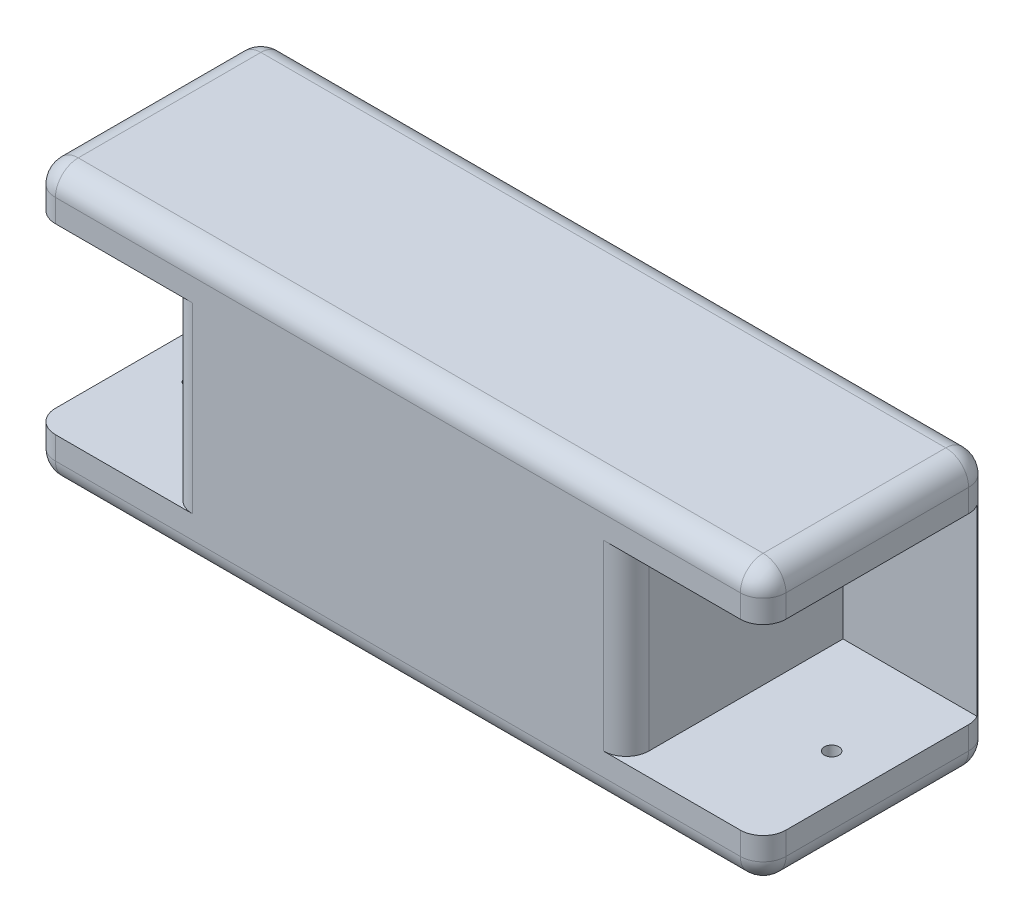
SolidWorks part; units mm, degrees
ref_plane "Front Plane" through (0, 0, 0) normal (0, 0, 1) x (1, 0, 0)
ref_plane "Top Plane" through (0, 0, 0) normal (0, 1, 0) x (1, 0, 0)
ref_plane "Right Plane" through (0, 0, 0) normal (1, 0, 0) x (0, 0, -1)
sketch "Sketch2" plane through (0, 0, 0) normal (0, 0, 1) x (1, 0, 0)
  line L1 (-80, 30) -> (80, 30)
  line L2 (-80, 30) -> (-80, -30)
  line L3 (-80, -30) -> (80, -30)
  line L4 (80, 30) -> (80, -30)
  line L5 (-80, 30) -> (80, -30) construction
  line L6 (-80, -30) -> (80, 30) construction
  point P0 (0, 0)
  dimension "D1" = 160
  dimension "D2" = 60
extrude "Boss-Extrude1" add sketch "Sketch2" along normal blind 50
sketch "Sketch4" plane through (0, 0, 50) normal (0, 0, 1) x (1, 0, 0)
  line L0 (-80, 0) -> (80, 0) construction
  line L1 (-80, 30) -> (-80, -30) construction
  line L2 (80, -30) -> (80, 30) construction
  line L3 (-80, -30) -> (80, -30) construction
  line L4 (80, 20) -> (50, 20)
  line L5 (80, 20) -> (80, -20)
  line L6 (80, -20) -> (50, -20)
  line L7 (50, 20) -> (50, -20)
  line L8 (80, 30) -> (-80, 30) construction
  line L9 (0, 30) -> (0, -30) construction
  line L12 (-80, 20) -> (-50, 20)
  line L13 (-80, 20) -> (-80, -20)
  line L14 (-80, -20) -> (-50, -20)
  line L15 (-50, 20) -> (-50, -20)
  dimension "D1" = 30
  dimension "D2" = 10
  dimension "D3" = 10
  dimension "D4" = 30
  dimension "D5" = 40
  dimension "D6" = 10
  dimension "D7" = 10
extrude "Cut-Extrude1" cut sketch "Sketch4" against normal through all
sketch "Sketch5" plane through (0, 20, 0) normal (0, -1, 0) x (-1, 0, 0)
  line L0 (80, -50) -> (80, 0) construction
  line L1 (80, -25) -> (-80, -25) construction
  line L2 (-80, -50) -> (-80, 0) construction
  line L3 (0, 0) -> (0, -50) construction
  line L4 (80, -50) -> (-80, -50) construction
  circle A0 centre (70, -25) radius 1.6
  dimension "D1" = 10
  dimension "D2" = 3.2
extrude "Cut-Extrude2" cut sketch "Sketch5" against normal blind 3.2
sketch "Sketch6" plane through (0, -20, 0) normal (0, 1, 0) x (1, 0, 0)
  line L0 (-80, -25) -> (80, -25) construction
  line L1 (-80, -50) -> (-80, 0) construction
  line L2 (80, -50) -> (80, 0) construction
  circle A0 centre (-70, -25) radius 1.6
  dimension "D1" = 10
  dimension "D2" = 3.2
extrude "Cut-Extrude3" cut sketch "Sketch6" against normal blind 3.2
sketch "Sketch7" plane through (0, 30, 0) normal (0, 1, 0) x (1, 0, 0)
  line L0 (-80, -25) -> (80, -25) construction
  line L1 (-80, -50) -> (-80, 0) construction
  line L2 (80, -50) -> (80, 0) construction
  circle A0 centre (70, -25) radius 1.6
  dimension "D1" = 10
  dimension "D2" = 3.2
extrude "Cut-Extrude5" cut sketch "Sketch7" against normal blind 3.2 from offset 6.8 offset against normal yes
sketch "Sketch8" plane through (0, -30, 0) normal (0, -1, 0) x (1, 0, 0)
  line L0 (-80, 25) -> (80, 25) construction
  line L1 (-80, 50) -> (-80, 0) construction
  line L2 (80, 50) -> (80, 0) construction
  circle A0 centre (70, 25) radius 1.6
  dimension "D1" = 3.2
  dimension "D2" = 10
extrude "Cut-Extrude6" cut sketch "Sketch8" against normal blind 3.2 from offset 6.8 offset against normal yes
sketch "Sketch9" plane through (-50, 0, 0) normal (-1, 0, 0) x (0, 0, 1)
  line L0 (0, -20) -> (50, -20) construction
  line L1 (0, 20) -> (2.5, 20)
  line L2 (0, 20) -> (0, -20)
  line L3 (0, -20) -> (2.5, -20)
  line L4 (2.5, 20) -> (2.5, -20)
  dimension "D1" = 2.5
extrude "Boss-Extrude2" add sketch "Sketch9" along normal blind 30
sketch "Sketch10" plane through (50, 0, 0) normal (1, 0, 0) x (0, 0, -1)
  line L0 (0, -20) -> (-50, -20) construction
  line L1 (0, 20) -> (-2.5, 20)
  line L2 (0, 20) -> (0, -20)
  line L3 (0, -20) -> (-2.5, -20)
  line L4 (-2.5, 20) -> (-2.5, -20)
  dimension "D1" = 2.5
extrude "Boss-Extrude3" add sketch "Sketch10" along normal blind 30
fillet "Fillet1" radius 5 16 edges at (-80, -25, 50) (-80, 25, 50) (80, 25, 50) (80, -25, 50) (50, 0, 50) (80, -30, 25) (80, 30, 25) (80, 0, 0) (0, 30, 0) (0, -30, 0) (0, -30, 50) (-80, -30, 25) (-80, 0, 0) (-80, 30, 25) (-50, 0, 50) (0, 30, 50)
